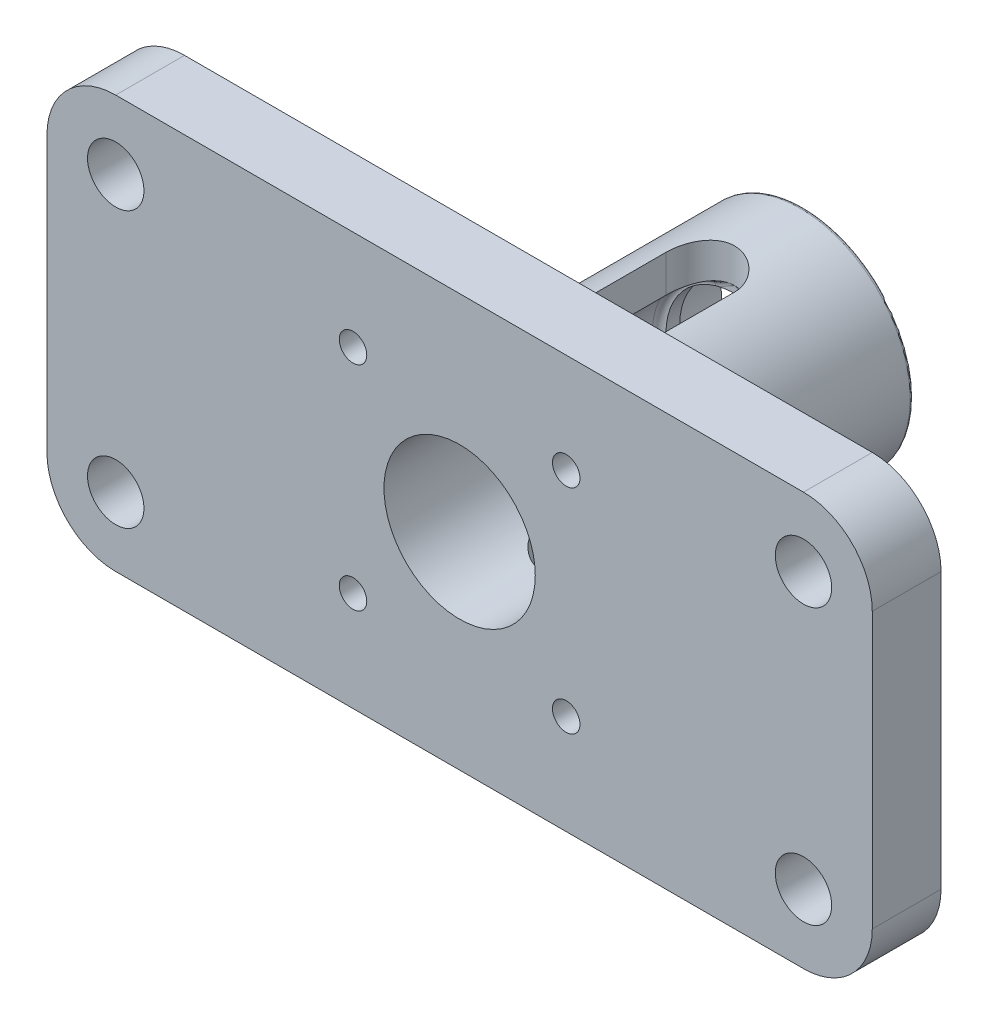
SolidWorks part; units mm, degrees
ref_plane "Alzado" through (0, 0, 0) normal (0, 0, 1) x (1, 0, 0)
ref_plane "Planta" through (0, 0, 0) normal (0, 1, 0) x (1, 0, 0)
ref_plane "Vista lateral" through (0, 0, 0) normal (1, 0, 0) x (0, 0, -1)
sketch "Croquis1" plane through (0, 0, 0) normal (0, 0, 1) x (1, 0, 0)
  line L0 (0, 30) -> (0, -30) construction
  line L1 (-60, 30) -> (60, 30)
  line L2 (-60, 30) -> (-60, -30)
  line L3 (-60, -30) -> (60, -30)
  line L4 (60, 30) -> (60, -30)
  line L5 (15.5, 0) -> (-15.5, 0) construction
  line L6 (-15.5, -15.5) -> (15.5, -15.5) construction
  line L7 (-15.5, -15.5) -> (-15.5, 15.5) construction
  line L8 (-15.5, 15.5) -> (15.5, 15.5) construction
  line L9 (15.5, -15.5) -> (15.5, 15.5) construction
  circle A0 centre (-15.5, 15.5) radius 2
  circle A1 centre (15.5, 15.5) radius 2
  circle A2 centre (15.5, -15.5) radius 2
  circle A3 centre (-15.5, -15.5) radius 2
  circle A4 centre (0, 0) radius 11
  dimension "D3" = 22
  dimension "D6" = 4
  dimension "D1" = 120
  dimension "D2" = 60
  dimension "D4" = 31
  dimension "D5" = 31
extrude "Saliente-Extruir1" add sketch "Croquis1" against normal blind 10
fillet "Redondeo1" radius 10 4 edges at (60, 30, -5) (60, -30, -5) (-60, 30, -5) (-60, -30, -5)
sketch "Croquis2" plane through (0, 0, -10) normal (0, 0, -1) x (-1, 0, 0)
  circle A0 centre (0, 0) radius 11
  circle A1 centre (0, 0) radius 16
  dimension "D1" = 32
  dimension "D2" = 22
extrude "Saliente-Extruir2" add sketch "Croquis2" along normal blind 40
ref_plane "Plano1" through (0, 0, -42) normal (0, 0, -1) x (-1, 0, 0)
sketch "Croquis3" plane through (0, 0, -42) normal (0, 0, -1) x (-1, 0, 0)
  circle A0 centre (0, 0) radius 11
  circle A1 centre (0, 0) radius 10
  dimension "D1" = 22
  dimension "D2" = 20
extrude "Saliente-Extruir3" add sketch "Croquis3" against normal blind 2
fillet "Redondeo2" radius 0.5 2 edges at (-11, 0, -50) (-16, 0, -50)
hole_wizard "Taladro de margen para M81" positions "Croquis5" profile "Croquis4" hole size "M8" standard "Ansi Metric"
sketch "Croquis5" plane through (0, 0, -10) normal (0, 0, -1) x (-1, 0, 0)
  point P0 (-50, 20)
  point P3 (50, 20)
  point P6 (50, -20)
  point P9 (-50, -20)
sketch "Croquis4" plane through (50, 20, -10) normal (1, 0, 0) x (0, 1, 0)
  line L0 (0, 0) -> (0, 202.4635)
  line L1 (0, 202.4635) -> (4.1, 200)
  line L2 (4.1, 200) -> (4.1, 0)
  line L5 (4.1, 0) -> (0, 0)
  line L10 (0, 202.4635) -> (-4.1, 200) construction
  line L11 (0, -6.35) -> (0, 107.95) construction
  dimension "Diámetro de taladro" = 8.2
  dimension "Profundidad de taladro" = 200
  dimension "Ángulo de perforador" = 118
sketch "Croquis6" plane through (0, 0, 0) normal (0, 1, 0) x (1, 0, 0)
  line L0 (0, 35) -> (0, 17) construction
  line L1 (5, 35) -> (5, 17)
  line L2 (-5, 35) -> (-5, 17)
  line L3 (11.5, 50) -> (-11.5, 50) construction
  arc A0 (5, 35) -> (-5, 35) centre (0, 35) ccw
  arc A1 (-5, 17) -> (5, 17) centre (0, 17) ccw
  point P3 (0, 26)
  dimension "D3" = 15
  dimension "D1" = 10
  dimension "D2" = 18
extrude "Cortar-Extruir1" cut sketch "Croquis6" against normal mid plane 60
sketch "Croquis7" plane through (0, 0, -50) normal (0, 0, -1) x (-1, 0, 0)
  circle A0 centre (0, 0) radius 12
  dimension "D1" = 24
extrude "Cortar-Extruir2" cut sketch "Croquis7" against normal blind 8
fillet "Redondeo3" radius 1 1 edges at (16, 0, -10)
fillet "Redondeo5" radius 1 2 edges at (-11, 0, -40) (11, 0, -40)
